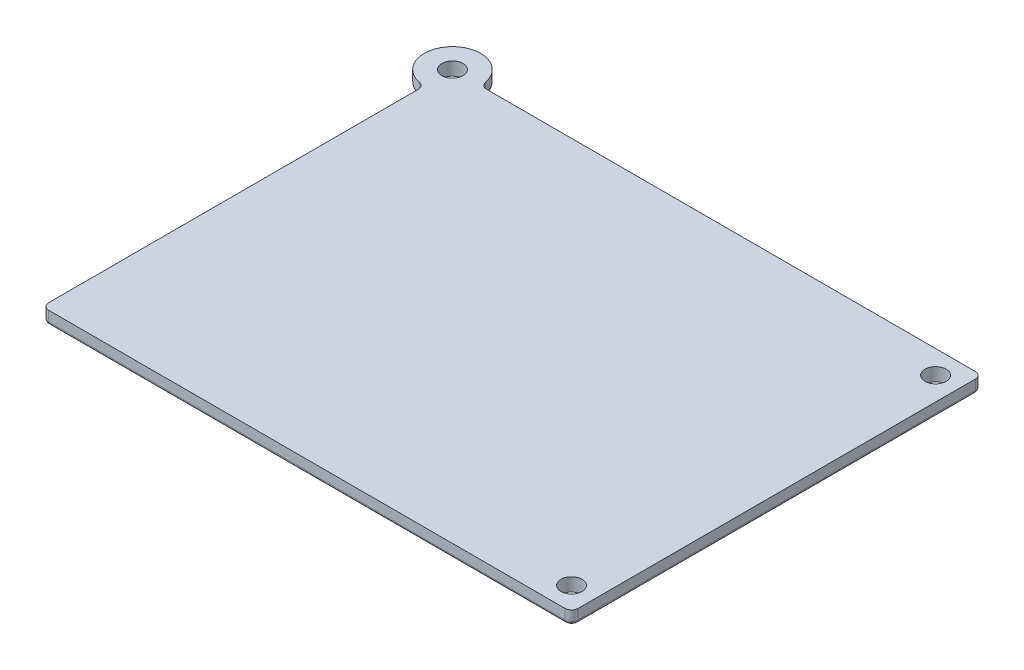
SolidWorks part; units mm, degrees
material "PVC Rigid"
ref_plane "Front Plane" through (0, 0, 0) normal (0, 0, 1) x (1, 0, 0)
ref_plane "Top Plane" through (0, 0, 0) normal (0, 1, 0) x (1, 0, 0)
ref_plane "Right Plane" through (0, 0, 0) normal (1, 0, 0) x (0, 0, -1)
sketch "Sketch1" plane through (0, 0, 0) normal (0, 1, 0) x (1, 0, 0)
  line L1 (-40, -31) -> (40, -31)
  line L2 (-40, -31) -> (-40, 25.8461)
  line L3 (-34.8461, 31) -> (40, 31)
  line L4 (40, -31) -> (40, 31)
  line L5 (-40, -31) -> (40, 31) construction
  line L6 (0, 0) -> (40, -31) construction
  arc A0 (-40, 25.8461) -> (-40.8095, 26.8278) centre (-41, 25.8461) ccw construction
  arc A1 (-35.8278, 31.8095) -> (-34.8461, 31) centre (-34.8461, 32) ccw construction
  arc A2 (-35.8278, 31.8095) -> (-40.8095, 26.8278) centre (-40, 31) ccw construction
  arc A3 (-40, 25.8461) -> (-40.8095, 26.8278) centre (-41, 25.8461) ccw
  arc A4 (-35.8278, 31.8095) -> (-34.8461, 31) centre (-34.8461, 32) ccw
  arc A5 (-35.8278, 31.8095) -> (-40.8095, 26.8278) centre (-40, 31) ccw
  point P0 (0, 0)
  dimension "D1" = 80
  dimension "D2" = 62
extrude "Main Body" add sketch "Sketch1" along normal blind 2
fillet "Corners" radius 1 3 edges at (-40, 1, 31) (40, 1, -31) (40, 1, 31)
fillet "Edge" radius 0.5 10 edges at (-39.7071, 0, 30.7071) (39.7071, 0, -30.7071) (39.7071, 0, 30.7071) (-40, 0, 2.0769) (2.0769, 0, -31) (40, 0, 0) (0, 0, 31) (-40.2285, 0, -26.4823) (-43.0052, 0, -34.0052) (-35.4823, 0, -31.2285)
sketch "Sketch7" plane through (0, 0, 0) normal (0, -1, 0) x (-1, 0, 0)
  line L0 (-39, 31) -> (34.8461, 31) construction
  line L1 (-40, -30) -> (-40, 30) construction
  circle A0 centre (-36.5, 27.5) radius 1.6
  circle A1 centre (-36.5, -27.5) radius 1.6
  circle A4 centre (40, 31) radius 1.6
  circle A5 centre (40, 31) radius 1.6 construction
  dimension "D1" = 3.5
  dimension "D2" = 3.5
  dimension "D3" = 3.2
  dimension "D4" = 3.2
extrude "Lid Holes" cut sketch "Sketch7" against normal through all both and the other way through all
sketch "Peg Angle" plane through (0, 0, 0) normal (0, -1, 0) x (-1, 0, 0)
  line L0 (39.5, -30) -> (19.4082, -13.9542) construction
  line L1 (-39.3536, -30.3536) -> (-19.8872, -10.8872) construction
  arc A0 (-39.5, -30) -> (-39, -30.5) centre (-39, -30) ccw construction
sketch "Sketch4" plane through (0, 0, 0) normal (0, -1, 0) x (-1, 0, 0)
  line L0 (-39.3536, -30.3536) -> (-19.8872, -10.8872) construction
  line L3 (-34.4038, -19.747) -> (-28.747, -25.4038) construction
  circle A0 centre (-34.4038, -19.747) radius 2.325
  circle A1 centre (-28.747, -25.4038) radius 2.325
  point P8 (-31.5754, -22.5754)
  dimension "D1" = 4.65
  dimension "D3" = 4.65
  dimension "D2" = 4
  dimension "D4" = 8
  dimension "D5" = 11
extrude "Boss-Extrude3" add sketch "Sketch4" along normal blind 1.6
fillet "Fillet3" radius 0.05 2 edges at (34.4038, -1.6, 17.422) (28.747, -1.6, 23.0788)
pattern_linear "LPattern5" count 4 spacing 8 along (-0.7071, 0, -0.7071) of "Boss-Extrude3", "Fillet3"
sketch "Sketch9" plane through (0, 0, 0) normal (0, -1, 0) x (-1, 0, 0)
  line L0 (39.5, -30) -> (19.4082, -13.9542) construction
  line L2 (27.317, -25.3894) -> (32.3093, -19.1383) construction
  circle A0 centre (27.317, -25.3894) radius 2.325
  circle A1 centre (32.3093, -19.1383) radius 2.325
  arc A2 (39, -31) -> (40, -30) centre (39, -30) ccw construction
  point P8 (29.8131, -22.2639)
  point P11 (39.7071, -30.7071)
  dimension "D1" = 4.65
  dimension "D2" = 4.65
  dimension "D3" = 8
  dimension "D4" = 13
extrude "Pegs (Diagonal)" add sketch "Sketch9" along normal blind 1.6
fillet "Fillet6" radius 0.05 2 edges at (-27.317, -1.6, 23.0644) (-32.3093, -1.6, 16.8133)
pattern_linear "LPattern6" count 4 spacing 8 along (0.7814, 0, -0.624) of "Pegs (Diagonal)"
equation "\"D2@Sketch9\"=\"D1@Sketch9\""
equation "\"D3@Sketch4\"=\"D1@Sketch4\""
equation "\"D4@Sketch4\"=\"D2@Sketch4\"*2"
